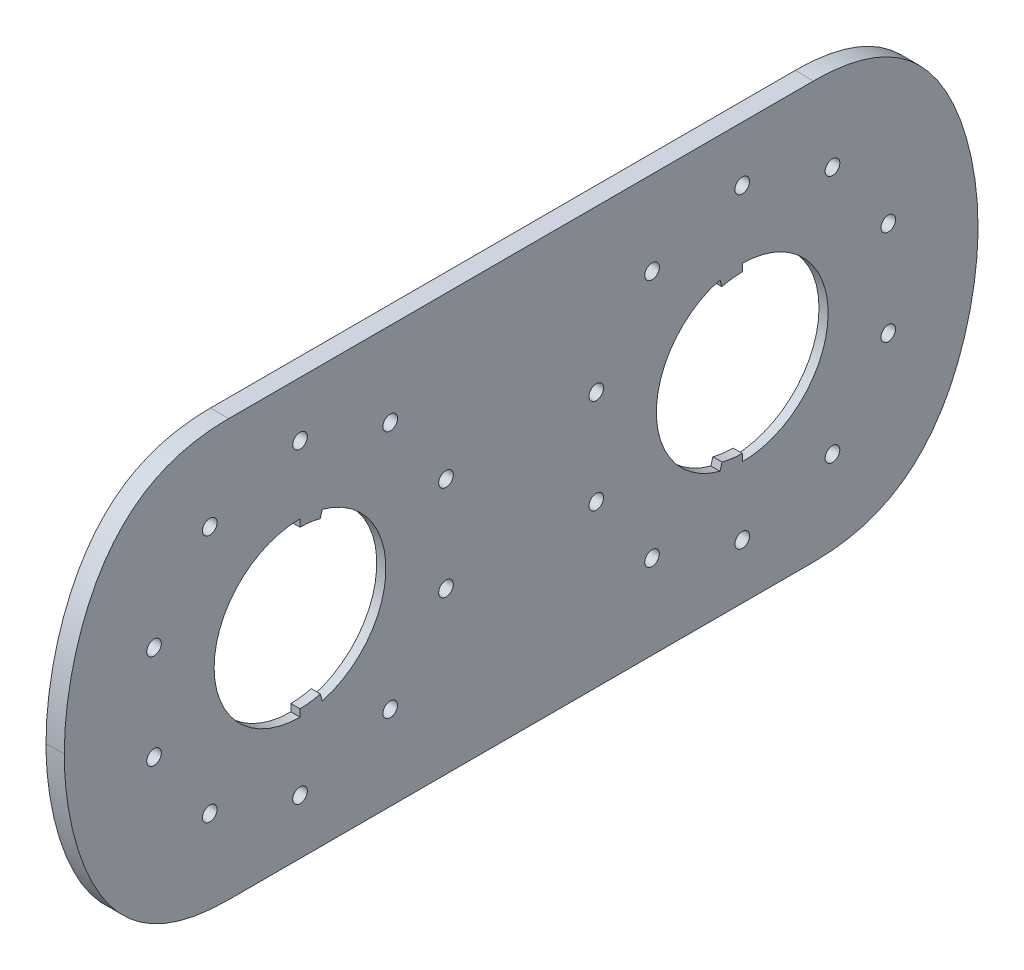
SolidWorks part; units mm, degrees
ref_plane "前视基准面" through (0, 0, 0) normal (0, 0, 1) x (1, 0, 0)
ref_plane "上视基准面" through (0, 0, 0) normal (0, 1, 0) x (1, 0, 0)
ref_plane "右视基准面" through (0, 0, 0) normal (1, 0, 0) x (0, 0, -1)
sketch "草图1" plane through (0, 0, 0) normal (1, 0, 0) x (0, 0, -1)
  line L0 (0, 57) -> (80, 57)
  line L1 (80, -57) -> (0, -57)
  line L2 (0, 57) -> (0, -57)
  line L3 (80, 57) -> (110.7152, 57) construction
  line L4 (110.7152, 57) -> (118.0231, 36.993) construction
  line L5 (118.0231, 36.993) -> (125, 20.498) construction
  line L6 (125, 20.498) -> (125, 0) construction
  line L7 (0, 0) -> (125, 0) construction
  line L8 (80, -57) -> (110.7152, -57) construction
  line L9 (110.7152, -57) -> (118.0231, -36.993) construction
  line L10 (118.0231, -36.993) -> (125, -20.498) construction
  line L11 (125, -20.498) -> (125, 0) construction
  circle A0 centre (60.5, 0) radius 48 construction
  spline S0 degree 4 poles (80, 57) (110.7152, 57) (118.0231, 36.993) (125, 20.498) (125, 0) knots 0 0 0 0 0 1 1 1 1 1
  spline S1 degree 4 poles (80, -57) (110.7152, -57) (118.0231, -36.993) (125, -20.498) (125, 0) knots 0 0 0 0 0 1 1 1 1 1
  dimension "D1" = 60.5
  dimension "D2" = 96
  dimension "D4" = 125
  dimension "D3" = 57
  dimension "D6" = 80
extrude "凸台-拉伸1" add sketch "草图1" along normal blind 5
sketch "草图2" plane through (0, 0, 0) normal (-1, 0, 0) x (0, 0, 1)
  circle A0 centre (-60.5, 0) radius 31
  dimension "D1" = 60.5
  dimension "D2" = 62
extrude "切除-拉伸1" cut sketch "草图2" against normal blind 2.5
sketch "草图3" plane through (0, 0, 0) normal (-1, 0, 0) x (0, 0, 1)
  line L0 (-60.5, 0) -> (-60.5, 79.1647) construction
  line L1 (-60.5, 0) -> (-60.5, 42) construction
  circle A1 centre (-60.5, 42) radius 2
  dimension "D1" = 0
  dimension "D2" = 42
  dimension "D3" = 4
extrude "切除-拉伸2" cut sketch "草图3" against normal up to next
pattern_circular "阵列(圆周)1" count 10 over 360 about axis through (0, 0, -60.5) along (-1, 0, 0) of "切除-拉伸2"
sketch "草图4" plane through (2.5, 0, 0) normal (-1, 0, 0) x (0, 0, 1)
  circle A0 centre (-60.5, 0) radius 23.5
  dimension "D1" = 47
extrude "切除-拉伸3" cut sketch "草图4" against normal up to next
sketch "草图5" plane through (5, 0, 0) normal (1, 0, 0) x (0, 0, -1)
  circle A0 centre (60.5, 0) radius 34.5
  circle A1 centre (60.5, 0) radius 37.5
  dimension "D1" = 75
  dimension "D2" = 69
sketch "草图7" plane through (0, 0, 0) normal (-1, 0, 0) x (0, 0, 1)
  line L0 (-60.5, 48) -> (-81.7662, 48)
  line L1 (-60.5, -48) -> (-81.7662, -48)
  arc A0 (-60.5, 48) -> (-60.5, -48) centre (-60.5, 0) ccw
  arc A1 (-81.7662, 48) -> (-81.7662, -48) centre (-60.5, 0) ccw
  dimension "D1" = 96
  dimension "D2" = 105
sketch "草图8" plane through (5, 0, 0) normal (1, 0, 0) x (0, 0, -1)
  line L0 (54.9354, 20.7674) -> (54.4178, 22.6993)
  line L1 (60.5, 21.5) -> (60.5, 23.5)
  line L2 (60.5, 0) -> (0, 0) construction
  line L3 (60.5, -21.5) -> (60.5, -23.5)
  line L4 (54.9354, -20.7674) -> (54.4178, -22.6993)
  circle A0 centre (60.5, 0) radius 23.5 construction
  arc A1 (60.5, 23.5) -> (54.4178, 22.6993) centre (60.5, 0) ccw
  arc A2 (60.5, 21.5) -> (54.9354, 20.7674) centre (60.5, 0) ccw
  arc A3 (60.5, -21.5) -> (54.9354, -20.7674) centre (60.5, 0) cw
  arc A4 (60.5, -23.5) -> (54.4178, -22.6993) centre (60.5, 0) cw
  dimension "D1" = 43
  dimension "D2" = 15
extrude "凸台-拉伸3" add sketch "草图8" against normal up to surface (2.5 mm away) up to face at (2.5, 0, -37)
mirror "镜向3" about plane through (5, 57, 0) normal (0, 0, -1) of bodies 122 114
